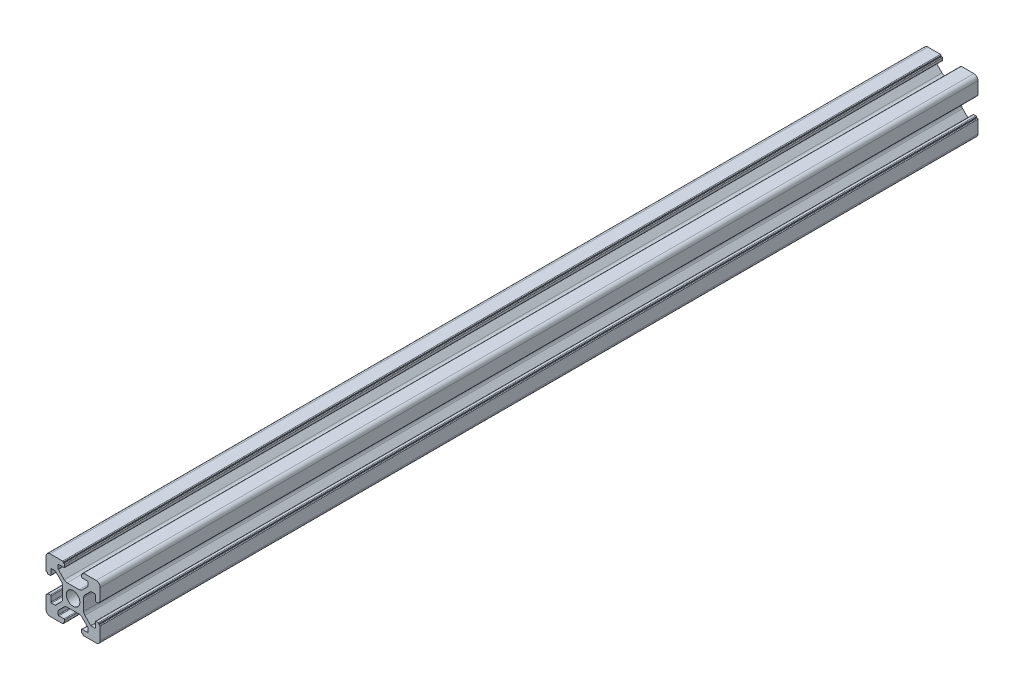
SolidWorks part; units mm, degrees
ref_plane "前视基准面" through (0, 0, 0) normal (0, 0, 1) x (1, 0, 0)
ref_plane "上视基准面" through (0, 0, 0) normal (0, 1, 0) x (1, 0, 0)
ref_plane "右视基准面" through (0, 0, 0) normal (1, 0, 0) x (0, 0, -1)
sketch "草图1" plane through (0, 0, 0) normal (0, 0, 1) x (1, 0, 0)
  line L0 (0, 0) -> (0, 5.5) construction
  line L1 (-8.5023, -10.0023) -> (-3.85, -10.0023)
  line L2 (-10.0023, -8.5023) -> (-10.0023, -3.85)
  line L3 (-8.5023, 10.0023) -> (-3.85, 10.0023)
  line L4 (10.0023, -8.5023) -> (10.0023, -3.85)
  line L5 (-10.0023, -10.0023) -> (10.0023, 10.0023) construction
  line L6 (-10.0023, 10.0023) -> (10.0023, -10.0023) construction
  line L7 (-2.218, -3.9) -> (2.218, -3.9)
  line L8 (-3.9, -2.218) -> (-3.9, 2.218)
  line L9 (-2.218, 3.9) -> (2.218, 3.9)
  line L10 (3.9, -2.218) -> (3.9, 2.218)
  line L11 (-3.9, -3.9) -> (3.9, 3.9) construction
  line L12 (-3.9, 3.9) -> (3.9, -3.9) construction
  line L13 (-5.25, -8.2) -> (-3.35, -8.2)
  line L14 (-8.2, -5.25) -> (-8.2, -3.35)
  line L15 (-5.25, 8.2) -> (-3.35, 8.2)
  line L16 (8.2, -5.25) -> (8.2, -3.35)
  line L17 (-8.2, -8.2) -> (8.2, 8.2) construction
  line L18 (-8.2, 8.2) -> (8.2, -8.2) construction
  line L19 (-7.95, 5.5) -> (-6.6642, 5.5)
  line L20 (0, 0) -> (5.5, 0) construction
  line L23 (-5.5, 7.95) -> (-5.5, 6.6642)
  line L26 (0, 0) -> (-0.5303, 0.5303)
  line L27 (3.2787, 4.3393) -> (5.4268, 6.4874)
  line L28 (0, 0) -> (0.5303, -0.5303)
  line L29 (5.5, 6.6642) -> (5.5, 7.95)
  line L30 (4.3393, 3.2787) -> (6.4874, 5.4268)
  line L31 (6.6642, 5.5) -> (7.95, 5.5)
  line L32 (4.3393, -3.2787) -> (6.4874, -5.4268)
  line L33 (3.2787, -4.3393) -> (5.4268, -6.4874)
  line L34 (-3.2787, -4.3393) -> (-5.4268, -6.4874)
  line L35 (-4.3393, -3.2787) -> (-6.4874, -5.4268)
  line L36 (-4.3393, 3.2787) -> (-6.4874, 5.4268)
  line L37 (-3.2787, 4.3393) -> (-5.4268, 6.4874)
  line L38 (3.1, -8.45) -> (3.1, -9.2523)
  line L39 (8.45, 3.1) -> (9.2523, 3.1)
  line L40 (-5.5, -6.6642) -> (-5.5, -7.95)
  line L41 (-6.6642, -5.5) -> (-7.95, -5.5)
  line L42 (5.5, -6.6642) -> (5.5, -7.95)
  line L43 (6.6642, -5.5) -> (7.95, -5.5)
  line L44 (9.2523, -3.1) -> (8.45, -3.1)
  line L46 (10.0023, 3.85) -> (10.0023, 8.5023)
  line L47 (8.2, 3.35) -> (8.2, 5.25)
  line L48 (-3.1, -9.2523) -> (-3.1, -8.45)
  line L49 (-8.45, -3.1) -> (-9.2523, -3.1)
  line L50 (-9.2523, 3.1) -> (-8.45, 3.1)
  line L51 (-3.1, 8.45) -> (-3.1, 9.2523)
  line L52 (3.1, 9.2523) -> (3.1, 8.45)
  line L53 (3.85, 10.0023) -> (8.5023, 10.0023)
  line L54 (3.35, 8.2) -> (5.25, 8.2)
  line L55 (-10.0023, 3.85) -> (-10.0023, 8.5023)
  line L56 (-8.2, 3.35) -> (-8.2, 5.25)
  line L57 (3.35, -8.2) -> (5.25, -8.2)
  line L58 (3.85, -10.0023) -> (8.5023, -10.0023)
  line L59 (9.7523, -3.6) -> (9.5023, -3.6)
  line L61 (9.7523, 3.6) -> (9.5023, 3.6)
  line L62 (9.5023, -3.6) -> (9.5023, -3.35)
  line L63 (3.6, -9.7523) -> (3.6, -9.5023)
  line L64 (3.35, -9.5023) -> (3.6, -9.5023)
  line L65 (9.5023, 3.35) -> (9.5023, 3.6)
  line L66 (-3.6, -9.5023) -> (-3.35, -9.5023)
  line L67 (-3.6, -9.7523) -> (-3.6, -9.5023)
  line L68 (-9.7523, -3.6) -> (-9.5023, -3.6)
  line L69 (-9.5023, -3.35) -> (-9.5023, -3.6)
  line L70 (-9.5023, 3.6) -> (-9.5023, 3.35)
  line L71 (-9.7523, 3.6) -> (-9.5023, 3.6)
  line L72 (-3.6, 9.7523) -> (-3.6, 9.5023)
  line L73 (-3.35, 9.5023) -> (-3.6, 9.5023)
  line L74 (3.6, 9.5023) -> (3.35, 9.5023)
  line L75 (3.6, 9.7523) -> (3.6, 9.5023)
  circle A0 centre (0, 0) radius 2.5
  arc A1 (10.0023, 8.5023) -> (8.5023, 10.0023) centre (8.5023, 8.5023) ccw
  arc A2 (8.5023, -10.0023) -> (10.0023, -8.5023) centre (8.5023, -8.5023) ccw
  arc A3 (-10.0023, -8.5023) -> (-8.5023, -10.0023) centre (-8.5023, -8.5023) ccw
  arc A4 (-10.0023, 8.5023) -> (-8.5023, 10.0023) centre (-8.5023, 8.5023) cw
  arc A5 (-9.5023, -3.35) -> (-9.2523, -3.1) centre (-9.2523, -3.35) cw
  arc A6 (-9.7523, -3.6) -> (-10.0023, -3.85) centre (-9.7523, -3.85) ccw
  arc A7 (-8.45, -3.1) -> (-8.2, -3.35) centre (-8.45, -3.35) cw
  arc A8 (-7.95, -5.5) -> (-8.2, -5.25) centre (-7.95, -5.25) cw
  arc A9 (-6.4874, -5.4268) -> (-6.6642, -5.5) centre (-6.6642, -5.25) cw
  arc A10 (-5.4268, -6.4874) -> (-5.5, -6.6642) centre (-5.25, -6.6642) ccw
  arc A11 (-5.5, -7.95) -> (-5.25, -8.2) centre (-5.25, -7.95) ccw
  arc A12 (-3.6, -9.7523) -> (-3.85, -10.0023) centre (-3.85, -9.7523) cw
  arc A13 (-3.35, -9.5023) -> (-3.1, -9.2523) centre (-3.35, -9.2523) ccw
  arc A14 (-3.1, -8.45) -> (-3.35, -8.2) centre (-3.35, -8.45) ccw
  arc A15 (3.1, -8.45) -> (3.35, -8.2) centre (3.35, -8.45) cw
  arc A16 (5.5, -7.95) -> (5.25, -8.2) centre (5.25, -7.95) cw
  arc A17 (5.4268, -6.4874) -> (5.5, -6.6642) centre (5.25, -6.6642) cw
  arc A18 (6.4874, -5.4268) -> (6.6642, -5.5) centre (6.6642, -5.25) ccw
  arc A19 (7.95, -5.5) -> (8.2, -5.25) centre (7.95, -5.25) ccw
  arc A20 (8.45, -3.1) -> (8.2, -3.35) centre (8.45, -3.35) ccw
  arc A21 (9.5023, -3.35) -> (9.2523, -3.1) centre (9.2523, -3.35) ccw
  arc A22 (9.7523, -3.6) -> (10.0023, -3.85) centre (9.7523, -3.85) cw
  arc A23 (3.35, -9.5023) -> (3.1, -9.2523) centre (3.35, -9.2523) cw
  arc A24 (3.6, -9.7523) -> (3.85, -10.0023) centre (3.85, -9.7523) ccw
  arc A25 (7.95, 5.5) -> (8.2, 5.25) centre (7.95, 5.25) cw
  arc A26 (8.2, 3.35) -> (8.45, 3.1) centre (8.45, 3.35) ccw
  arc A27 (9.5023, 3.35) -> (9.2523, 3.1) centre (9.2523, 3.35) cw
  arc A28 (9.7523, 3.6) -> (10.0023, 3.85) centre (9.7523, 3.85) ccw
  arc A29 (6.6642, 5.5) -> (6.4874, 5.4268) centre (6.6642, 5.25) ccw
  arc A30 (5.4268, 6.4874) -> (5.5, 6.6642) centre (5.25, 6.6642) ccw
  arc A31 (5.5, 7.95) -> (5.25, 8.2) centre (5.25, 7.95) ccw
  arc A32 (3.1, 8.45) -> (3.35, 8.2) centre (3.35, 8.45) ccw
  arc A33 (3.6, 9.7523) -> (3.85, 10.0023) centre (3.85, 9.7523) cw
  arc A34 (3.35, 9.5023) -> (3.1, 9.2523) centre (3.35, 9.2523) ccw
  arc A35 (-9.7523, 3.6) -> (-10.0023, 3.85) centre (-9.7523, 3.85) cw
  arc A36 (-9.5023, 3.35) -> (-9.2523, 3.1) centre (-9.2523, 3.35) ccw
  arc A37 (-8.45, 3.1) -> (-8.2, 3.35) centre (-8.45, 3.35) ccw
  arc A38 (-8.2, 5.25) -> (-7.95, 5.5) centre (-7.95, 5.25) cw
  arc A39 (-6.4874, 5.4268) -> (-6.6642, 5.5) centre (-6.6642, 5.25) ccw
  arc A40 (-5.4268, 6.4874) -> (-5.5, 6.6642) centre (-5.25, 6.6642) cw
  arc A41 (-5.5, 7.95) -> (-5.25, 8.2) centre (-5.25, 7.95) cw
  arc A42 (-3.1, 8.45) -> (-3.35, 8.2) centre (-3.35, 8.45) cw
  arc A43 (-3.1, 9.2523) -> (-3.35, 9.5023) centre (-3.35, 9.2523) ccw
  arc A44 (-3.6, 9.7523) -> (-3.85, 10.0023) centre (-3.85, 9.7523) ccw
  arc A45 (-4.3393, 3.2787) -> (-3.9, 2.218) centre (-5.4, 2.218) cw
  arc A46 (-3.2787, 4.3393) -> (-2.218, 3.9) centre (-2.218, 5.4) ccw
  arc A47 (3.2787, 4.3393) -> (2.218, 3.9) centre (2.218, 5.4) cw
  arc A48 (4.3393, 3.2787) -> (3.9, 2.218) centre (5.4, 2.218) ccw
  arc A49 (4.3393, -3.2787) -> (3.9, -2.218) centre (5.4, -2.218) cw
  arc A50 (3.2787, -4.3393) -> (2.218, -3.9) centre (2.218, -5.4) ccw
  arc A51 (-4.3393, -3.2787) -> (-3.9, -2.218) centre (-5.4, -2.218) ccw
  arc A52 (-2.218, -3.9) -> (-3.2787, -4.3393) centre (-2.218, -5.4) ccw
  point P0 (0, 0)
  point P7 (10.0023, 0)
  point P62 (0, 0)
  point P76 (0, 0)
  point P92 (-8.2, -5.5)
  point P99 (0, 0)
  point P106 (-5.5, -8.2)
  point P117 (5.5, -8.2)
  point P124 (8.2, -5.5)
  point P137 (8.2, 5.5)
  point P140 (8.2, 3.1)
  point P147 (6.5607, 5.5)
  point P152 (5.5, 8.2)
  point P167 (-8.2, 5.5)
  point P174 (-5.5, 8.2)
  dimension "D1" = 1.5
  dimension "D5" = 0.25
  dimension "D6" = 1.5
  dimension "D2" = 4
  dimension "D3" = 4
  dimension "D4" = 4
extrude "凸台-拉伸1" add sketch "草图1" along normal blind 324 contours A52 L7 A50 L33 A17 L42 A16 L57 A15 L38 A23 L64 L63 A24 L58 A2 L4 A22 L59 L62 A21 L44 A20 L16 A19 L43 A18 L32 A49 L10 A48 L30 A29 L31 A25 L47 A26 L39 A27 L65 L61 A28 L46 A1 L53 A33 L75 L74 A34 L52 A32 region at (-9.3629, -9.3629, 0)
